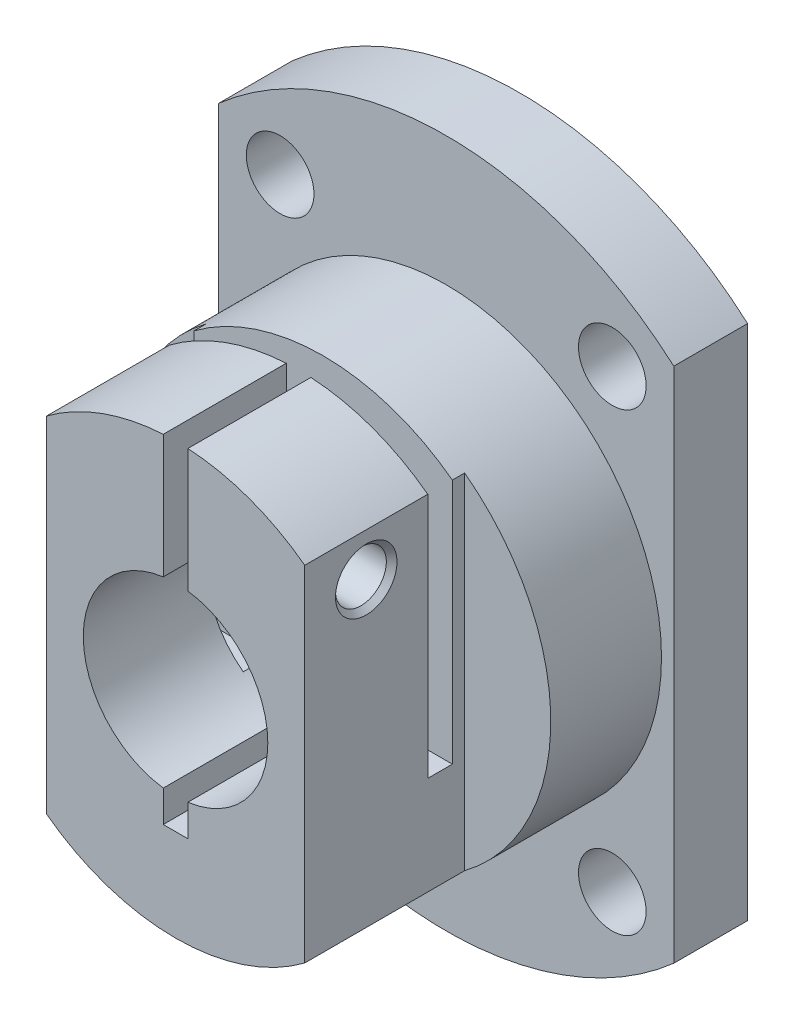
SolidWorks part; units mm, degrees
ref_plane "前视基准面" through (0, 0, 0) normal (0, 0, 1) x (1, 0, 0)
ref_plane "上视基准面" through (0, 0, 0) normal (0, 1, 0) x (1, 0, 0)
ref_plane "右视基准面" through (0, 0, 0) normal (1, 0, 0) x (0, 0, -1)
sketch "草图1" plane through (0, 0, 0) normal (0, 0, 1) x (1, 0, 0)
  circle A0 centre (0, 0) radius 28
extrude "凸台-拉伸1" add sketch "草图1" against normal blind 14 and the other way blind 14
ref_plane "基准面4" through (0, 0, -8) normal (0, 0, 1) x (1, 0, 0)
sketch "草图2" plane through (0, 0, -8) normal (0, 0, 1) x (1, 0, 0)
  circle A0 centre (0, 0) radius 112
  circle A1 centre (0, 0) radius 17.5
extrude "切除-拉伸1" cut sketch "草图2" along normal blind 22
sketch "草图3" plane through (0, 0, 0) normal (0, 0, 1) x (1, 0, 0)
  line L0 (18.5, 28) -> (18.5, -28)
  line L1 (18.5, -28) -> (53.5, -28)
  line L2 (53.5, -28) -> (53.5, 28)
  line L3 (53.5, 28) -> (18.5, 28)
extrude "切除-拉伸2" cut sketch "草图3" along normal blind 28 and the other way blind 28
sketch "草图4" plane through (0, 0, 0) normal (0, 0, 1) x (1, 0, 0)
  line L0 (-53.5, 28) -> (-53.5, -28)
  line L1 (-53.5, -28) -> (-18.5, -28)
  line L2 (-18.5, -28) -> (-18.5, 28)
  line L3 (-18.5, 28) -> (-53.5, 28)
extrude "切除-拉伸3" cut sketch "草图4" along normal blind 28 and the other way blind 28
ref_plane "基准面5" through (0, 0, 1) normal (0, 0, 1) x (1, 0, 0)
sketch "草图5" plane through (0, 0, 1) normal (0, 0, 1) x (1, 0, 0)
  line L0 (10.5, 17.5) -> (10.5, -17.5)
  line L1 (10.5, -17.5) -> (45.5, -17.5)
  line L2 (45.5, -17.5) -> (45.5, 17.5)
  line L3 (45.5, 17.5) -> (10.5, 17.5)
extrude "切除-拉伸4" cut sketch "草图5" along normal blind 28
sketch "草图6" plane through (0, 0, 1) normal (0, 0, 1) x (1, 0, 0)
  line L0 (-45.5, 17.5) -> (-45.5, -17.5)
  line L1 (-45.5, -17.5) -> (-10.5, -17.5)
  line L2 (-10.5, -17.5) -> (-10.5, 17.5)
  line L3 (-10.5, 17.5) -> (-45.5, 17.5)
extrude "切除-拉伸5" cut sketch "草图6" along normal blind 28
sketch "草图7" plane through (0, 0, -8) normal (0, 0, 1) x (1, 0, 0)
  circle A0 centre (-13.5, -18.5) radius 2.75
extrude "切除-拉伸6" cut sketch "草图7" against normal blind 6
sketch "草图8" plane through (0, 0, 0) normal (0, 0, 1) x (1, 0, 0)
  line L0 (-13.5, -18.5) -> (986.5, -18.5)
  line L1 (-13.5, -18.5) -> (-13.5, 981.5)
pattern_linear "阵列(线性)1" count 2 spacing 27 along (1, 0, 0) count 2 spacing 37 along (0, 1, 0) of "切除-拉伸6"
ref_plane "基准面6" through (0, 0, 14) normal (0, 0, 1) x (1, 0, 0)
sketch "草图9" plane through (0, 0, 14) normal (0, 0, 1) x (1, 0, 0)
  line L0 (-1, 35) -> (-1, -10)
  line L1 (-1, -10) -> (1, -10)
  line L2 (1, -10) -> (1, 35)
  line L3 (1, 35) -> (-1, 35)
extrude "切除-拉伸7" cut sketch "草图9" against normal blind 12
sketch "草图10" plane through (0, 0, 0) normal (1, 0, 0) x (0, 0, -1)
  line L0 (-4, 35) -> (-4, -6)
  line L1 (-4, -6) -> (-2, -6)
  line L2 (-2, -6) -> (-2, 35)
  line L3 (-2, 35) -> (-4, 35)
extrude "切除-拉伸8" cut sketch "草图10" along normal blind 35 and the other way blind 35
ref_plane "基准面7" through (0, 0, 9) normal (0, 0, 1) x (1, 0, 0)
sketch "草图11" plane through (0, 0, 9) normal (0, 0, 1) x (1, 0, 0)
  line L0 (-10.5, 10.5) -> (-10.5, 13)
  line L1 (-10.5, 13) -> (-10.067, 12.567)
  line L2 (-10.067, 12.567) -> (-1, 12.567)
  line L3 (-1, 12.567) -> (-1, 10.5)
  line L4 (-1, 10.5) -> (-10.5, 10.5)
  line L5 (-1, 10.5) -> (-10.5, 10.5) construction
revolve "切除-旋转1" cut sketch "草图11" angle 360 about L5 reverse direction yes
cosmetic thread "装饰螺纹线1" parameters "D1"=9.5, "D2"=5
sketch "草图12" plane through (0, 0, 9) normal (0, 0, 1) x (1, 0, 0)
  line L0 (1, 10.5) -> (1, 12.567)
  line L1 (1, 12.567) -> (10.067, 12.567)
  line L2 (10.067, 12.567) -> (10.5, 13)
  line L3 (10.5, 13) -> (10.5, 10.5)
  line L4 (10.5, 10.5) -> (1, 10.5)
  line L5 (10.5, 10.5) -> (1, 10.5) construction
revolve "切除-旋转2" cut sketch "草图12" angle 360 about L5 reverse direction yes
cosmetic thread "装饰螺纹线2" parameters "D1"=9.5, "D2"=5
sketch "草图13" plane through (0, 0, 0) normal (1, 0, 0) x (0, 0, -1)
  line L0 (-14, 0) -> (-14, 7.5)
  line L1 (-14, 7.5) -> (5, 7.5)
  line L2 (5, 7.5) -> (5, 14)
  line L3 (5, 14) -> (12, 14)
  line L4 (12, 14) -> (12, 15.05)
  line L5 (12, 15.05) -> (13.2, 15.05)
  line L6 (13.2, 15.05) -> (13.2, 14)
  line L7 (13.2, 14) -> (14, 14)
  line L8 (14, 14) -> (14, 0)
  line L9 (14, 0) -> (-14, 0)
  line L10 (14, 0) -> (-14, 0) construction
revolve "切除-旋转3" cut sketch "草图13" angle 360 about L10 reverse direction yes
ref_plane "基准面8" through (-10.5, 0, 0) normal (1, 0, 0) x (0, 0, -1)
ref_plane "基准面9" through (0, 0, -12) normal (0, 0, 1) x (1, 0, 0)
ref_plane "基准面10" through (0, 0, -14) normal (0, 0, 1) x (1, 0, 0)
ref_plane "基准面11" through (0, 0, -8) normal (0, 0, 1) x (1, 0, 0)
ref_plane "lever XY" through (-10.5, 0, 0) normal (1, 0, 0) x (0, 0, -1)
ref_plane "lever XZ" through (0, 10.5, 0) normal (0, -1, 0) x (-1, 0, 0)
ref_plane "lever YZ" through (0, 0, 9) normal (0, 0, -1) x (-1, 0, 0)
ref_axis "lever X" through (-10.5, 10.5, 80.9) along (0, 0, -1)
ref_axis "lever Y" through (-10.5, -50, 9) along (0, 1, 0)
ref_axis "lever Z" through (80.9, 10.5, 9) along (-1, 0, 0)
sketch3d "lever"
  point P0 (-10.5, 10.5, 9)
ref_plane "bearing_bushing_ring XY" through (0, 0, -12) normal (0, 0, 1) x (1, 0, 0)
ref_plane "bearing_bushing_ring XZ" through (0, 0, 0) normal (0, -1, 0) x (-1, 0, 0)
ref_plane "bearing_bushing_ring YZ" through (0, 0, 0) normal (1, 0, 0) x (0, 0, -1)
ref_axis "bearing_bushing_ring X" through (-80.9, 0, -12) along (1, 0, 0)
ref_axis "bearing_bushing_ring Y" through (0, -50, -12) along (0, 1, 0)
ref_axis "bearing_bushing_ring Z" through (0, 0, 80.9) along (0, 0, -1)
sketch3d "bearing_bushing_ring"
  point P0 (0, 0, -12)
ref_plane "stop_plate_to_frame_kue XY" through (0, 0, -14) normal (0, 0, 1) x (1, 0, 0)
ref_plane "stop_plate_to_frame_kue XZ" through (0, 0, 0) normal (0, -1, 0) x (-1, 0, 0)
ref_plane "stop_plate_to_frame_kue YZ" through (0, 0, 0) normal (1, 0, 0) x (0, 0, -1)
ref_axis "stop_plate_to_frame_kue X" through (-80.9, 0, -14) along (1, 0, 0)
ref_axis "stop_plate_to_frame_kue Y" through (0, -50, -14) along (0, 1, 0)
ref_axis "stop_plate_to_frame_kue Z" through (0, 0, 80.9) along (0, 0, -1)
sketch3d "stop_plate_to_frame_kue"
  point P0 (0, 0, -14)
ref_plane "to_bolt_2 XY" through (0, 0, -8) normal (0, 0, 1) x (1, 0, 0)
ref_plane "to_bolt_2 XZ" through (0, -18.5, 0) normal (0, -1, 0) x (-1, 0, 0)
ref_plane "to_bolt_2 YZ" through (13.5, 0, 0) normal (1, 0, 0) x (0, 0, -1)
ref_axis "to_bolt_2 X" through (-80.9, -18.5, -8) along (1, 0, 0)
ref_axis "to_bolt_2 Y" through (13.5, -50, -8) along (0, 1, 0)
ref_axis "to_bolt_2 Z" through (13.5, -18.5, 80.9) along (0, 0, -1)
sketch3d "to_bolt_2"
  point P0 (13.5, -18.5, -8)
ref_plane "to_bolt_3 XY" through (0, 0, -8) normal (0, 0, 1) x (1, 0, 0)
ref_plane "to_bolt_3 XZ" through (0, 18.5, 0) normal (0, -1, 0) x (-1, 0, 0)
ref_plane "to_bolt_3 YZ" through (-13.5, 0, 0) normal (1, 0, 0) x (0, 0, -1)
ref_axis "to_bolt_3 X" through (-80.9, 18.5, -8) along (1, 0, 0)
ref_axis "to_bolt_3 Y" through (-13.5, -50, -8) along (0, 1, 0)
ref_axis "to_bolt_3 Z" through (-13.5, 18.5, 80.9) along (0, 0, -1)
sketch3d "to_bolt_3"
  point P0 (-13.5, 18.5, -8)
ref_plane "to_bolt_1 XY" through (0, 0, -8) normal (0, 0, 1) x (1, 0, 0)
ref_plane "to_bolt_1 XZ" through (0, -18.5, 0) normal (0, -1, 0) x (-1, 0, 0)
ref_plane "to_bolt_1 YZ" through (-13.5, 0, 0) normal (1, 0, 0) x (0, 0, -1)
ref_axis "to_bolt_1 X" through (-80.9, -18.5, -8) along (1, 0, 0)
ref_axis "to_bolt_1 Y" through (-13.5, -50, -8) along (0, 1, 0)
ref_axis "to_bolt_1 Z" through (-13.5, -18.5, 80.9) along (0, 0, -1)
sketch3d "to_bolt_1"
  point P0 (-13.5, -18.5, -8)
ref_plane "to_bolt_4 XY" through (0, 0, -8) normal (0, 0, 1) x (1, 0, 0)
ref_plane "to_bolt_4 XZ" through (0, 18.5, 0) normal (0, -1, 0) x (-1, 0, 0)
ref_plane "to_bolt_4 YZ" through (13.5, 0, 0) normal (1, 0, 0) x (0, 0, -1)
ref_axis "to_bolt_4 X" through (-80.9, 18.5, -8) along (1, 0, 0)
ref_axis "to_bolt_4 Y" through (13.5, -50, -8) along (0, 1, 0)
ref_axis "to_bolt_4 Z" through (13.5, 18.5, 80.9) along (0, 0, -1)
sketch3d "to_bolt_4"
  point P0 (13.5, 18.5, -8)
